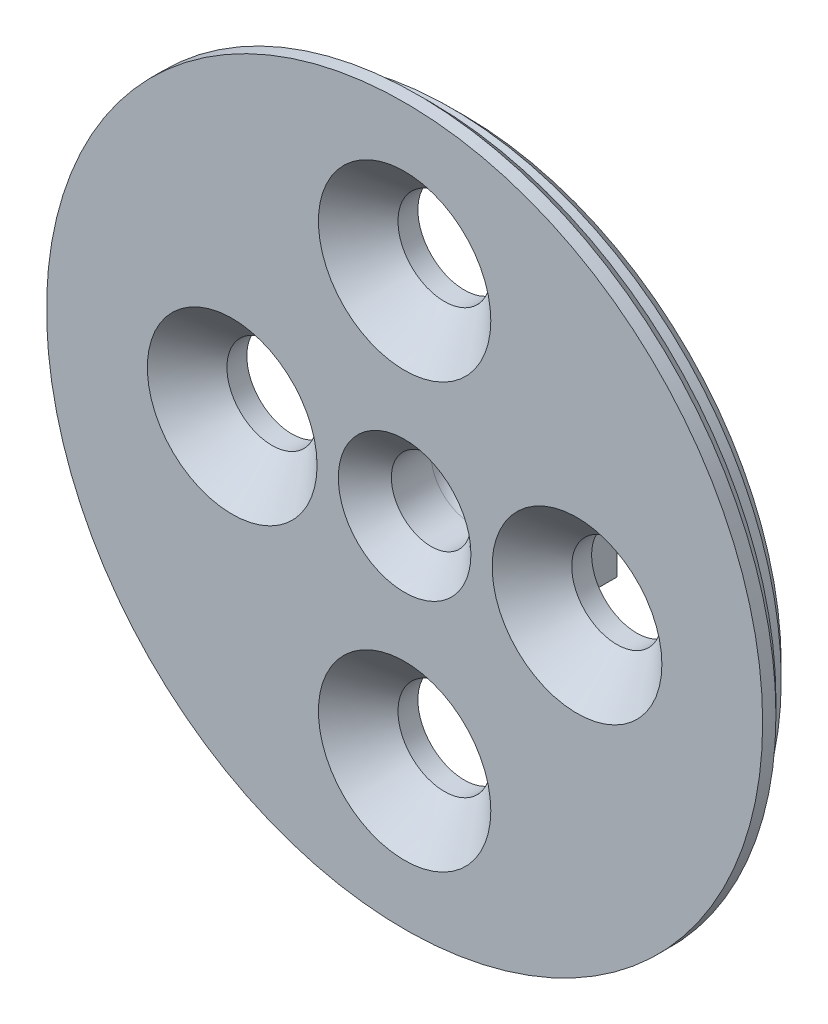
SolidWorks part; units mm, degrees
ref_plane "Front Plane" through (0, 0, 0) normal (0, 0, 1) x (1, 0, 0)
ref_plane "Top Plane" through (0, 0, 0) normal (0, 1, 0) x (1, 0, 0)
ref_plane "Right Plane" through (0, 0, 0) normal (1, 0, 0) x (0, 0, -1)
sketch "Sketch1" plane through (0, 0, 0) normal (0, 0, 1) x (1, 0, 0)
  line L0 (0, 9.3188) -> (0, -6.9028) construction
  circle A0 centre (0, 0) radius 12.45
  circle A1 centre (-6.5, 0) radius 1.7
  circle A2 centre (6.5, 0) radius 1.7
  dimension "D2" = 24.9
  dimension "D3" = 3.4
  dimension "D1" = 13
extrude "Boss-Extrude1" add sketch "Sketch1" against normal blind 1.25
sketch "Sketch2" plane through (0, 0, -1.25) normal (0, 0, -1) x (-1, 0, 0)
  line L1 (-2.75, 3.25) -> (2.75, 3.25)
  line L2 (-2.75, 3.25) -> (-2.75, -3.25)
  line L3 (-2.75, -3.25) -> (2.75, -3.25)
  line L4 (2.75, 3.25) -> (2.75, -3.25)
  line L5 (-2.75, 3.25) -> (2.75, -3.25) construction
  line L6 (-2.75, -3.25) -> (2.75, 3.25) construction
  point P0 (0, 0)
  dimension "D1" = 6.5
  dimension "D2" = 5.5
extrude "Boss-Extrude2" add sketch "Sketch2" along normal blind 3.5
sketch "Sketch3" plane through (0, 0, 0) normal (0, 0, 1) x (1, 0, 0)
  circle A0 centre (0, 0) radius 13.5
  circle A1 centre (-6.5, 0) radius 1.7
  circle A2 centre (6.5, 0) radius 1.7
  circle A3 centre (-6.5, 0) radius 1.7 construction
  dimension "D1" = 27
extrude "Boss-Extrude3" add sketch "Sketch3" along normal blind 1
chamfer "Chamfer1" distance 0.5 angle 45 5 edges at (0, 3.25, -4.75) (2.75, 0, -4.75) (0, -3.25, -4.75) (-2.75, 0, -4.75) (12.45, 0, -1.25)
sketch "Sketch5" plane through (0, 0, 1) normal (0, 0, 1) x (1, 0, 0)
  line L0 (0, 8) -> (0, -8) construction
  circle A0 centre (0, 8) radius 1.75
  circle A1 centre (0, -8) radius 1.75
  point P5 (0, 0)
  dimension "D2" = 3.5
  dimension "D1" = 16
extrude "Cut-Extrude2" cut sketch "Sketch5" against normal through all
chamfer "Chamfer3" distance 1.5 angle 45 4 edges at (8.2, 0, 1) (-4.8, 0, 1) (1.75, 8, 1) (1.75, -8, 1)
chamfer "Chamfer2" distance 0.5 angle 45 1 edges at (13.5, 0, 0)
sketch "Sketch6" plane through (0, 0, 1) normal (0, 0, 1) x (1, 0, 0)
  circle A0 centre (0, 0) radius 1.5
  dimension "D1" = 3
extrude "Cut-Extrude3" cut sketch "Sketch6" against normal blind 4
fillet "Fillet2" radius 1.5 1 edges at (1.5, 0, -3)
chamfer "Chamfer4" distance 1 angle 45 1 edges at (1.5, 0, 1)
